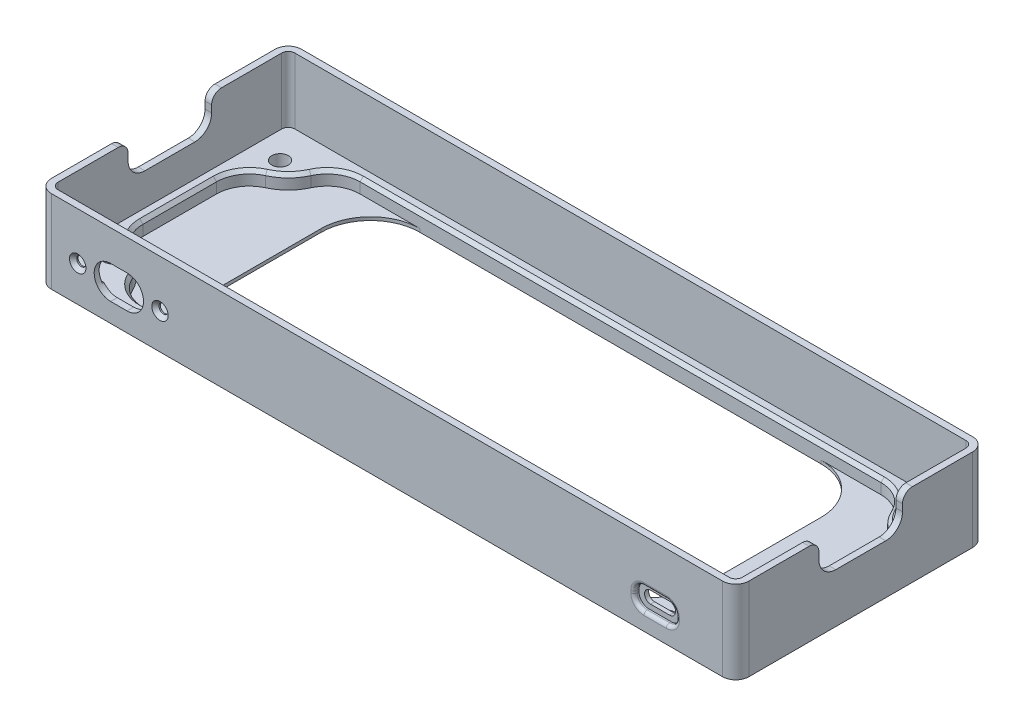
SolidWorks part; units mm, degrees
ref_plane "Front Plane" through (0, 0, 0) normal (0, 0, 1) x (1, 0, 0)
ref_plane "Top Plane" through (0, 0, 0) normal (0, 1, 0) x (1, 0, 0)
ref_plane "Right Plane" through (0, 0, 0) normal (1, 0, 0) x (0, 0, -1)
sketch "Sketch1" plane through (0, 0, 0) normal (0, 1, 0) x (1, 0, 0)
  line L1 (-102, -38) -> (102, -38)
  line L2 (-106, -34) -> (-106, 34)
  line L3 (-102, 38) -> (102, 38)
  line L4 (106, -34) -> (106, 34)
  line L5 (-106, -38) -> (106, 38) construction
  line L6 (-106, 38) -> (106, -38) construction
  line L7 (-101, -33) -> (101, -33)
  line L8 (-101, -33) -> (-101, 33)
  line L9 (-101, 33) -> (101, 33)
  line L10 (101, -33) -> (101, 33)
  line L11 (-101, -33) -> (101, 33) construction
  line L12 (-101, 33) -> (101, -33) construction
  arc A0 (-87, 33) -> (-101, 19) centre (-101, 33) cw
  arc A1 (-87, -33) -> (-101, -19) centre (-101, -33) ccw
  arc A2 (101, -19) -> (87, -33) centre (101, -33) ccw
  arc A3 (101, 19) -> (87, 33) centre (101, 33) cw
  arc A4 (102, 38) -> (106, 34) centre (102, 34) cw
  arc A5 (102, -38) -> (106, -34) centre (102, -34) ccw
  arc A6 (-102, -38) -> (-106, -34) centre (-102, -34) cw
  arc A7 (-106, 34) -> (-102, 38) centre (-102, 34) cw
  point P0 (0, 0)
  point P5 (0, 0)
  dimension "D5" = 14
  dimension "D6" = 4
  dimension "D1" = 212
  dimension "D2" = 76
  dimension "D3" = 5
  dimension "D4" = 5
extrude "Boss-Extrude1" add sketch "Sketch1" along normal blind 5.2 contours L1 L4 L3 L2 L10 L7 L8 L9 | A0 L9 L8 | L7 A1 L8 | L10 A2 L7 | A3 L10 L9 region at (-103.2359, 0, 35.2359) region at (-95.0582, 0, 27.0582) region at (95.0582, 0, 27.0582) region at (-95.0582, 0, -27.0582) region at (95.0582, 0, -27.0582)
fillet "Fillet1" radius 10 8 edges at (87, 2.6, 33) (101, 2.6, 19) (101, 2.6, -19) (87, 2.6, -33) (-87, 2.6, 33) (-101, 2.6, 19) (-87, 2.6, -33) (-101, 2.6, -19)
sketch "Sketch3" plane through (0, 0, 0) normal (0, -1, 0) x (-1, 0, 0)
  line L0 (102, 38) -> (-102, 38) construction
  line L1 (-102, -38) -> (-76, -38)
  line L2 (-106, -34) -> (-106, 34)
  line L3 (-102, 38) -> (-76, 38)
  line L4 (-76, -38) -> (-76, 38)
  line L5 (102, -38) -> (-102, -38) construction
  line L6 (102, -38) -> (76, -38)
  line L7 (106, -34) -> (106, 34)
  line L8 (102, 38) -> (76, 38)
  line L9 (76, -38) -> (76, 38)
  arc A0 (106, 34) -> (102, 38) centre (102, 34) ccw
  arc A1 (102, -38) -> (106, -34) centre (102, -34) ccw
  arc A2 (-102, -38) -> (-106, -34) centre (-102, -34) cw
  arc A3 (-106, 34) -> (-102, 38) centre (-102, 34) cw
  point P26 (106, -38)
  point P29 (-106, -38)
  dimension "D5" = 4
  dimension "D1" = 30
  dimension "D2" = 30
  dimension "D3" = 76
  dimension "D4" = 76
extrude "Boss-Extrude2" add sketch "Sketch3" against normal blind 1
sketch "Sketch2" plane through (0, 5.2, 0) normal (0, 1, 0) x (1, 0, 0)
  line L0 (-102, 38) -> (102, 38) construction
  line L1 (-106, -34) -> (-106, 34) construction
  line L2 (0, -11.44) -> (0, 11.44) construction
  line L3 (-11.44, 0) -> (11.44, 0) construction
  circle A0 centre (-96, 25.5) radius 2.5
  circle A1 centre (96, 25.5) radius 2.5
  circle A2 centre (96, -25.5) radius 2.5
  circle A3 centre (-96, -25.5) radius 2.5
  dimension "D1" = 12.5
  dimension "D3" = 5
  dimension "D2" = 10
extrude "Cut-Extrude1" cut sketch "Sketch2" against normal blind 5.2
sketch "Sketch4" plane through (0, 5.2, 0) normal (0, 1, 0) x (1, 0, 0)
  line L1 (-102, 38) -> (102, 38)
  line L2 (-106, 34) -> (-106, -34)
  line L3 (-102, -38) -> (102, -38)
  line L4 (106, 34) -> (106, -34)
  line L5 (102, -36) -> (-102, -36)
  line L6 (104, -34) -> (104, 34)
  line L7 (102, 36) -> (-102, 36)
  line L8 (-104, -34) -> (-104, 34)
  arc A0 (-102, -36) -> (-104, -34) centre (-102, -34) cw
  arc A1 (102, -36) -> (104, -34) centre (102, -34) ccw
  arc A2 (104, 34) -> (102, 36) centre (102, 34) ccw
  arc A3 (-102, 36) -> (-104, 34) centre (-102, 34) ccw
  arc A4 (102, 38) -> (106, 34) centre (102, 34) cw
  arc A5 (102, -38) -> (106, -34) centre (102, -34) ccw
  arc A6 (-106, -34) -> (-102, -38) centre (-102, -34) ccw
  arc A7 (-102, 38) -> (-106, 34) centre (-102, 34) ccw
  point P23 (106, -38)
  point P28 (-106, 38)
  dimension "D5" = 2
  dimension "D6" = 4
  dimension "D1" = 2
  dimension "D2" = 2
  dimension "D3" = 2
  dimension "D4" = 2
  dimension "D7" = 106
  dimension "D8" = 38
  dimension "D9" = 38
  dimension "D10" = 106
extrude "Boss-Extrude3" add sketch "Sketch4" along direction (0, 1, 0) on the side of the normal blind 20 contours L2 A6 L3 A5 L4 A4 L1 A7 | L6 A2 L7 A3 L8 A0 L5 A1
sketch "Sketch7" plane through (0, 0, 36) normal (0, 0, -1) x (-1, 0, 0)
  line L1 (-89.39, 15.2) -> (-73.61, 15.2)
  line L2 (-89.39, 15.2) -> (-89.39, 5.2)
  line L3 (-89.39, 5.2) -> (-73.61, 5.2)
  line L4 (-73.61, 15.2) -> (-73.61, 5.2)
  line L5 (-102, 5.2) -> (102, 5.2) construction
  line L6 (-106, 25.2) -> (-106, 0) construction
  dimension "D1" = 16.61
  dimension "D2" = 15.78
  dimension "D3" = 10
extrude "Boss-Extrude5" add sketch "Sketch7" along normal blind 0.75
sketch "Sketch6" plane through (0, 0, 38) normal (0, 0, 1) x (1, 0, 0)
  line L0 (84.39, 10.34) -> (78.61, 10.34)
  line L1 (74.28, 6.68) -> (88.72, 6.68) construction
  line L2 (74.28, 6.68) -> (74.28, 10.34) construction
  line L3 (74.28, 10.34) -> (88.72, 10.34) construction
  line L4 (88.72, 6.68) -> (88.72, 10.34) construction
  line L5 (74.28, 6.68) -> (88.72, 10.34) construction
  line L6 (74.28, 10.34) -> (88.72, 6.68) construction
  line L7 (106, 25.2) -> (106, 0) construction
  line L9 (78.61, 6.68) -> (84.39, 6.68)
  line L10 (-102, 0) -> (102, 0) construction
  arc A0 (78.61, 10.34) -> (78.61, 6.68) centre (78.61, 8.51) ccw
  arc A1 (84.39, 10.34) -> (84.39, 6.68) centre (84.39, 8.51) cw
  point P0 (81.5, 8.51)
  dimension "D1" = 24.5
  dimension "D2" = 14.44
  dimension "D3" = 8.51
  dimension "D4" = 3.66
  dimension "D5" = 2.89
  dimension "D6" = 2.89
extrude "Cut-Extrude2" cut sketch "Sketch6" against normal blind 10
sketch "Sketch8" plane through (0, 0, 38) normal (0, 0, 1) x (1, 0, 0)
  line L0 (84.39, 10.34) -> (78.61, 10.34) construction
  line L1 (78.11, 11.84) -> (84.89, 11.84)
  line L2 (75.11, 8.84) -> (75.11, 8.18)
  line L3 (78.11, 5.18) -> (84.89, 5.18)
  line L4 (87.89, 8.84) -> (87.89, 8.18)
  line L5 (78.61, 6.68) -> (84.39, 6.68) construction
  arc A0 (84.39, 6.68) -> (84.39, 10.34) centre (84.39, 8.51) ccw construction
  arc A1 (78.61, 10.34) -> (78.61, 6.68) centre (78.61, 8.51) ccw construction
  arc A2 (84.89, 11.84) -> (87.89, 8.84) centre (84.89, 8.84) cw
  arc A3 (84.89, 5.18) -> (87.89, 8.18) centre (84.89, 8.18) ccw
  arc A4 (75.11, 8.18) -> (78.11, 5.18) centre (78.11, 8.18) ccw
  arc A5 (78.11, 11.84) -> (75.11, 8.84) centre (78.11, 8.84) ccw
  dimension "D3" = 3.5
  dimension "D4" = 3.5
  dimension "D5" = 3
  dimension "D1" = 1.5
  dimension "D2" = 1.5
extrude "Cut-Extrude3" cut sketch "Sketch8" against normal blind 1.5
fillet "Fillet6" radius 1 8 edges at (87.89, 8.51, 38) (87.0113, 6.0587, 38) (81.5, 5.18, 38) (75.9887, 6.0587, 38) (75.11, 8.51, 38) (75.9887, 10.9613, 38) (81.5, 11.84, 38) (87.0113, 10.9613, 38)
chamfer "Chamfer1" distance 1 angle 45 2 edges at (89.39, 10.2, 35.25) (73.61, 10.2, 35.25)
sketch "Sketch9" plane through (0, 0, 38) normal (0, 0, 1) x (1, 0, 0)
  line L0 (-84, 10.81) -> (-79, 10.81) construction
  line L1 (-84, 15.81) -> (-79, 15.81)
  line L2 (-84, 5.81) -> (-79, 5.81)
  line L3 (-102, 0) -> (102, 0) construction
  line L4 (-106, 25.2) -> (-106, 0) construction
  arc A0 (-84, 15.81) -> (-84, 5.81) centre (-84, 10.81) ccw
  arc A1 (-79, 5.81) -> (-79, 15.81) centre (-79, 10.81) ccw
  point P2 (-81.5, 10.81)
  dimension "D3" = 5
  dimension "D1" = 10.81
  dimension "D2" = 5
  dimension "D4" = 24.5
extrude "Cut-Extrude4" cut sketch "Sketch9" against normal blind 3
sketch "Sketch11" plane through (0, 0, 38) normal (0, 0, 1) x (1, 0, 0)
  line L0 (-79, 15.81) -> (-84, 15.81) construction
  circle A0 centre (-94, 10.81) radius 1.4
  circle A1 centre (-69, 10.81) radius 1.4
  arc A2 (-84, 15.81) -> (-84, 5.81) centre (-84, 10.81) ccw construction
  dimension "D3" = 2.8
  dimension "D1" = 25
  dimension "D2" = 5
  dimension "D4" = 10
extrude "Cut-Extrude5" cut sketch "Sketch11" against normal blind 3.5
chamfer "Chamfer2" distance 1.1 angle 45 2 edges at (-67.6, 10.81, 38) (-92.6, 10.81, 38)
sketch "Sketch12" plane through (0, 0, 36) normal (0, 0, -1) x (-1, 0, 0)
  line L0 (69, 10.81) -> (94, 10.81) construction
  line L1 (69, 13.81) -> (94, 13.81)
  line L2 (69, 7.81) -> (94, 7.81)
  arc A0 (69, 13.81) -> (69, 7.81) centre (69, 10.81) ccw
  arc A1 (94, 7.81) -> (94, 13.81) centre (94, 10.81) ccw
  point P2 (81.5, 10.81)
  dimension "D1" = 3
extrude "Cut-Extrude6" cut sketch "Sketch12" against normal blind 0.5
chamfer "Chamfer3" distance 1 angle 45 16 edges at (-99.4163, 5.2, -16.5832) (-91.1005, 5.2, -23.1005) (-101, 5.2, 0) (-84.5832, 5.2, -31.4163) (-99.4163, 5.2, 16.5832) (0, 5.2, -33) (-91.1005, 5.2, 23.1005) (84.5832, 5.2, -31.4163) (-84.5832, 5.2, 31.4163) (91.1005, 5.2, -23.1005) (0, 5.2, 33) (99.4163, 5.2, -16.5832) (84.5832, 5.2, 31.4163) (101, 5.2, 0) (91.1005, 5.2, 23.1005) (99.4163, 5.2, 16.5832)
sketch "Sketch13" plane through (106, 0, 0) normal (1, 0, 0) x (0, 0, -1)
  line L0 (34, 25.2) -> (-34, 25.2) construction
  line L1 (-12.7, 15) -> (12.7, 15)
  line L2 (-12.7, 15) -> (-12.7, 25.2)
  line L3 (-12.7, 25.2) -> (12.7, 25.2)
  line L4 (12.7, 15) -> (12.7, 25.2)
  line L5 (-12.7, 15) -> (12.7, 25.2) construction
  line L6 (-12.7, 25.2) -> (12.7, 15) construction
  point P0 (0, 20.1)
  dimension "D1" = 5.1
  dimension "D2" = 25.4
extrude "Cut-Extrude7" cut sketch "Sketch13" against normal through all
fillet "Fillet7" radius 5.1 4 edges at (-105, 15, 12.7) (-105, 15, -12.7) (105, 15, -12.7) (105, 15, 12.7)
fillet "Fillet8" radius 3 4 edges at (-105, 25.2, 12.7) (-105, 25.2, -12.7) (105, 25.2, 12.7) (105, 25.2, -12.7)
fillet "Fillet9" radius 15 4 edges at (-76, 0.5, -33) (76, 0.5, -33) (76, 0.5, 33) (-76, 0.5, 33)
